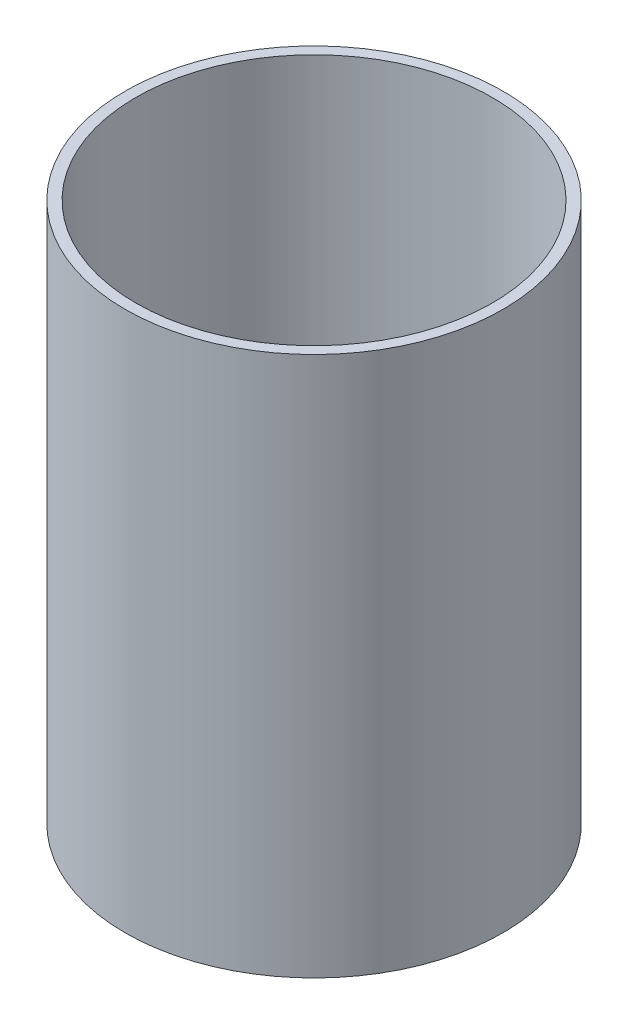
SolidWorks part; units mm, degrees
material "Melamine resin"
ref_plane "Front Plane" through (0, 0, 0) normal (0, 0, 1) x (1, 0, 0)
ref_plane "Top Plane" through (0, 0, 0) normal (0, 1, 0) x (1, 0, 0)
ref_plane "Right Plane" through (0, 0, 0) normal (1, 0, 0) x (0, 0, -1)
sketch "Sketch1" plane through (0, 0, 0) normal (0, 1, 0) x (1, 0, 0)
  circle A0 centre (0, 0) radius 17.5
  circle A1 centre (0, 0) radius 16.5
  dimension "D1" = 35
  dimension "D2" = 1
extrude "Boss-Extrude1" add sketch "Sketch1" along normal blind 50
extrude "Boss-Extrude2" add sketch "Sketch1<2>" along normal blind 2 contours A1 | A0 A1 region at (-17.005, 0, 0) region at (0, 0, 0)
sketch "Sketch1<2>" plane through (0, 0, 0) normal (0, 1, 0) x (1, 0, 0) same geometry as "Sketch1"
